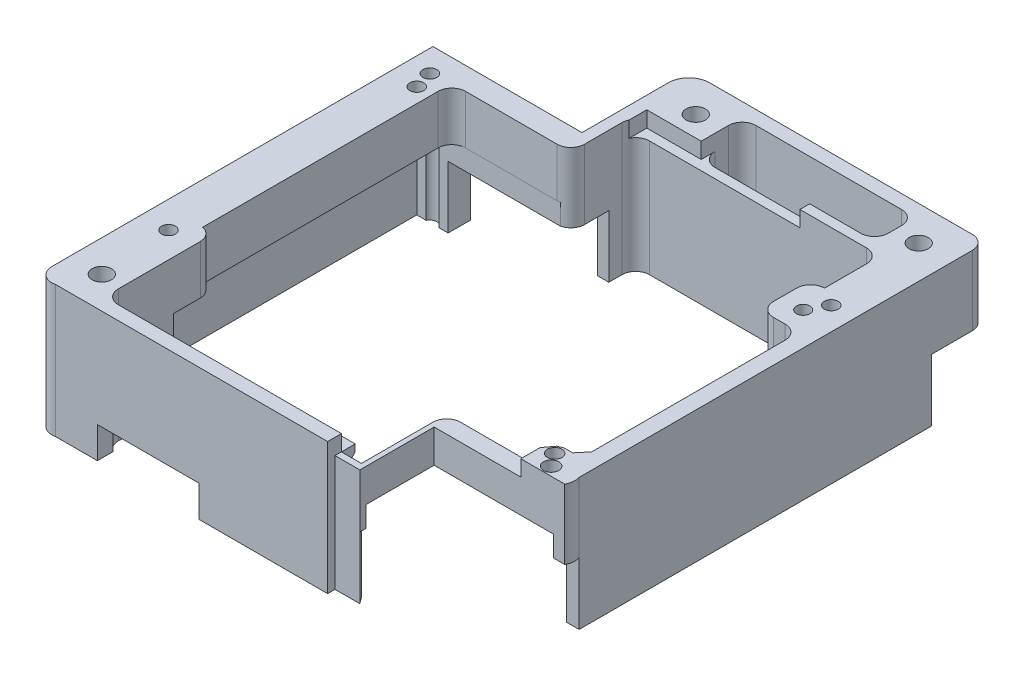
SolidWorks part; units mm, degrees
ref_plane "Спереди" through (0, 0, 0) normal (0, 0, 1) x (1, 0, 0)
ref_plane "Сверху" through (0, 0, 0) normal (0, 1, 0) x (1, 0, 0)
ref_plane "Справа" through (0, 0, 0) normal (1, 0, 0) x (0, 0, -1)
sketch "Sketch1" plane through (0, 0.1, 0) normal (0, -1, 0) x (1, 0, 0)
  line L0 (30.1923, -35.75) -> (30.1923, 21.25)
  line L1 (29.9933, 23.1419) -> (23.6204, 23.1419)
  line L2 (23.6204, 23.1419) -> (23.6204, 20.34)
  line L3 (23.6204, 20.34) -> (24.6552, 18.9626)
  line L4 (24.6552, 18.9626) -> (25.4, 18.6447)
  line L5 (25.4, 18.6447) -> (26.6442, 18.6447)
  line L6 (26.6442, 18.6447) -> (27.9, 17.1414)
  line L7 (27.9, 17.1414) -> (27.9, -12.9201)
  line L8 (27.9, -12.9201) -> (22.1982, -12.9201)
  line L9 (22.1982, -12.9201) -> (22.1982, -15.1177)
  line L10 (22.1982, -15.1177) -> (-28.5, -15.1177)
  line L14 (-28.5, -15.1177) -> (-28.5, 17.1414)
  line L15 (-28.5, 17.1414) -> (-26.8807, 17.1414)
  line L16 (-26.8807, 17.1414) -> (-26.8807, 26.25)
  line L17 (-26.8807, 26.25) -> (-26.8807, 34.9854)
  line L18 (-26.8807, 34.9854) -> (-31.9734, 34.9854)
  line L19 (-34.4999, 32.9854) -> (-34.5, -22.2395)
  line L20 (-34.5, -22.2395) -> (-12.89, -22.2395)
  line L21 (-12.89, -22.2395) -> (-12.89, -37.75)
  line L22 (-12.89, -37.75) -> (28.1923, -37.75)
  circle A0 centre (25.4, -32.7663) radius 1.4
  circle A1 centre (-6.9188, -32.7663) radius 1.4
  circle A2 centre (-29.9119, 30.3479) radius 1.4
  circle A3 centre (25.4, -16.0261) radius 0.9786
  circle A4 centre (-30.6214, -16.0261) radius 1
  circle A5 centre (25.4, 20.0142) radius 1.0496
  circle A6 centre (-30.6214, 19.9695) radius 1
  arc A7 (30.1923, -35.75) -> (28.1923, -37.75) centre (28.1923, -35.75) cw
  arc A8 (30.1923, 21.25) -> (29.9933, 23.1419) centre (27.8433, 21.9594) ccw
  arc A9 (-31.9734, 34.9854) -> (-34.4999, 32.9854) centre (-32.4675, 33.0137) ccw
  circle A10 centre (26.85, -18.6299) radius 1
  circle A11 centre (-31.3341, -18.6299) radius 1
  circle A13 centre (26.7535, 21.8701) radius 1.1
extrude "Boss-Extrude1" add sketch "Sketch1" along normal blind 3 and the other way blind 7.1
sketch "Sketch2" plane through (0, -2.9, 0) normal (0, -1, 0) x (1, 0, 0)
  line L0 (-26.8807, 17.1414) -> (-26.8807, 34.9854) construction
  line L2 (-26.8807, 34.9854) -> (-31.9734, 34.9854) construction
  line L8 (-26.8807, 32.9854) -> (-26.8807, 34.9854)
  line L14 (-26.8807, 34.9854) -> (7.4639, 34.9854)
  line L15 (7.4639, 34.9854) -> (7.4639, 32.9854)
  line L16 (7.4639, 32.9854) -> (-26.8807, 32.9854)
extrude "Boss-Extrude2" add sketch "Sketch2" against normal blind 10.1
sketch "Sketch5" plane through (0, 7.2, 0) normal (0, 1, 0) x (1, 0, 0)
  line L1 (-9.7084, -32.9854) -> (7.4639, -32.9854)
  line L2 (-9.7084, -32.9854) -> (-9.7084, -30.9854)
  line L3 (-9.7084, -30.9854) -> (7.4639, -30.9854)
  line L4 (7.4639, -32.9854) -> (7.4639, -30.9854)
extrude "Boss-Extrude5" add sketch "Sketch5" against normal blind 1 from offset 2.3 offset against normal yes
chamfer "Chamfer2" distance 2 angle 45 1 edges at (-1.1222, 3.9, 32.9854)
sketch "Sketch6" plane through (0, 7.2, 0) normal (0, 1, 0) x (1, 0, 0)
  line L2 (-11.0548, 29.8047) -> (-11.0548, 27.1518)
  line L7 (12.5536, 29.8047) -> (12.5536, 27.1518)
  line L12 (12.5536, 29.8047) -> (-11.0548, 29.8047)
  line L13 (-11.0548, 27.1518) -> (12.5536, 27.1518)
sketch "Sketch7" plane through (0, -2.9, 0) normal (0, -1, 0) x (1, 0, 0)
  line L0 (22.1982, -15.1177) -> (22.1982, -20.2902)
  line L1 (22.1982, -20.2902) -> (24.222, -20.2902)
  line L2 (24.222, -20.2902) -> (24.222, -28.3884)
  line L3 (22.1982, -15.1177) -> (-28.5, -15.1177) construction
  line L4 (22.1982, -12.9201) -> (22.1982, -15.1177) construction
  line L5 (24.222, -28.3884) -> (-11.2487, -28.3884)
  line L6 (-11.2487, -28.3884) -> (-11.2487, -18.9784)
  line L7 (-11.2487, -18.9784) -> (-28.5, -18.9784)
  line L9 (-28.5, -18.9784) -> (-28.5, -15.1177)
  line L10 (21.9508, -35.75) -> (21.9508, -29.8047)
  line L13 (21.9508, -29.8047) -> (-3.1678, -29.8047)
  line L14 (-3.1678, -29.8047) -> (-3.1678, -35.75)
  line L15 (-3.1678, -35.75) -> (21.9508, -35.75)
  line L16 (22.1982, -15.1177) -> (-28.5, -15.1177)
  dimension "D1" = 1.4163
extrude "Cut-Extrude1" cut sketch "Sketch7" against normal blind 21
extrude "Cut-Extrude2" cut sketch "Sketch6" against normal blind 2.3
sketch "Sketch8" plane through (0, -2.9, 0) normal (0, -1, 0) x (1, 0, 0)
  line L0 (23.6204, 23.1419) -> (11.0609, 23.1419)
  line L2 (11.0609, 23.1419) -> (11.0609, 33.9142)
  line L3 (11.0609, 33.9142) -> (7.4639, 33.9142)
  line L6 (7.4639, 33.9142) -> (7.4639, 32.9854)
  line L7 (7.4639, 32.9854) -> (10.3622, 32.9854)
  line L8 (10.3622, 32.9854) -> (10.3622, 20.6256)
  line L9 (10.3622, 20.6256) -> (23.6204, 20.6256)
  line L11 (23.6204, 20.6256) -> (23.6204, 23.1419)
  line L12 (7.4639, 32.9854) -> (7.4639, 34.9854) construction
  line L13 (29.9933, 23.1419) -> (23.6204, 23.1419) construction
  point P2 (11.0609, 23.1419)
extrude "Boss-Extrude6" add sketch "Sketch8" against normal up to surface (7.8 mm away) up to face at (-1.1222, 4.9, 31.9854)
fillet "Fillet1" radius 2 14 edges at (-28.5, 2.15, -18.9784) (21.9508, 2.15, -29.8047) (-3.1678, 1, -29.8047) (-3.1678, 2.15, -35.75) (21.9508, 2.15, -35.75) (22.1982, 2.15, -20.2902) (24.222, 2.15, -28.3884) (-11.2487, 2.15, -28.3884) (-11.2487, 2.15, -18.9784) (-26.8807, 2.15, 17.1414) (-26.8807, 2.15, 32.9854) (10.3622, 1, 20.6256) (22.1982, 2.15, -12.9201) (27.9, 2.15, -12.9201)
fillet "Fillet2" radius 3 1 edges at (-12.89, 2.15, -37.75)
sketch "Sketch9" plane through (0, -2.9, 0) normal (0, -1, 0) x (1, 0, 0)
  line L0 (-33.6214, 22.9739) -> (9.8918, 22.9739)
  line L1 (28.3786, -19.0261) -> (-33.6214, -19.0261)
  line L2 (28.3786, -19.0261) -> (28.3786, 22.9739)
  line L4 (-33.6214, -19.0261) -> (-33.6214, 22.9739)
  line L5 (9.8918, 22.9739) -> (9.8918, 32.9854)
  line L6 (9.8918, 32.9854) -> (28.3786, 32.9854)
  line L7 (28.3786, 32.9854) -> (28.3786, 22.9739)
  line L8 (-24.8807, 32.9854) -> (10.3622, 32.9854) construction
  circle A0 centre (-30.6214, -16.0261) radius 1 construction
  point P9 (9.8918, 32.9854)
  dimension "D1" = 62
  dimension "D2" = 42
  dimension "D3" = 3
  dimension "D4" = 3
extrude "Cut-Extrude3" cut sketch "Sketch9" against normal blind 3
sketch "Sketch10" plane through (0, -2.9, 0) normal (0, -1, 0) x (1, 0, 0)
  line L0 (30.1923, -29.8047) -> (-12.89, -29.8047)
  line L1 (30.1923, -35.75) -> (30.1923, 21.25) construction
  line L2 (-12.89, -22.2395) -> (-12.89, -34.75) construction
  line L3 (-12.89, -29.8047) -> (-12.89, -24.4887)
  line L5 (-34.5, -22.2395) -> (-34.4999, 32.9854)
  line L7 (-31.9734, 34.9854) -> (7.4639, 34.9854)
  line L8 (7.4639, 34.9854) -> (7.4639, 33.9142)
  line L9 (7.4639, 33.9142) -> (11.0609, 33.9142)
  line L12 (-30.416, -19.0261) -> (-12.8146, -19.0261) construction
  line L15 (30.1923, 21.25) -> (30.1923, -29.8047)
  line L16 (-33.6214, 22.9739) -> (-33.6214, -19.0261) construction
  line L17 (-29.0773, -19.0261) -> (-30.416, -19.0261)
  line L18 (-32.2523, -19.0261) -> (-33.6214, -19.0261)
  line L19 (10.3622, 32.9854) -> (11.0609, 33.9142)
  line L20 (30.1923, 21.25) -> (28.3786, 21.25)
  line L22 (28.3786, -19.0261) -> (28.3786, 23.1419) construction
  line L23 (28.3786, 21.25) -> (28.3786, -20.2902)
  line L24 (28.3786, -20.2902) -> (24.222, -20.2902)
  line L25 (24.222, -20.2902) -> (24.222, -26.3884)
  line L31 (-9.2487, -28.3884) -> (22.222, -28.3884)
  line L42 (10.3622, 32.9854) -> (10.3622, 23.3444) construction
  line L44 (-24.8807, 32.9854) -> (11.0609, 32.9854) construction
  line L45 (10.3622, 32.9854) -> (-24.8807, 32.9854)
  line L46 (-26.8807, 30.9854) -> (-26.8807, 28.6248)
  line L47 (-26.8807, 22.9739) -> (-26.8807, 30.9854) construction
  line L48 (-26.8807, 28.6248) -> (-33.6214, 28.6248)
  line L49 (-33.6214, 28.6248) -> (-33.6214, -19.0261)
  line L52 (-29.0773, -19.0261) -> (-29.0773, -22.2395)
  line L53 (-34.5, -22.2395) -> (-29.0773, -22.2395)
  line L54 (-11.2487, -26.3884) -> (-11.2487, -24.4887)
  line L55 (-11.2487, -20.9784) -> (-11.2487, -26.3884) construction
  line L56 (-11.2487, -24.4887) -> (-12.89, -24.4887)
  arc A1 (-34.4999, 32.9854) -> (-31.9734, 34.9854) centre (-32.4675, 33.0137) cw
  arc A2 (-30.416, -19.0261) -> (-32.2523, -19.0261) centre (-31.3341, -18.6299) cw
  arc A12 (22.222, -28.3884) -> (24.222, -26.3884) centre (22.222, -26.3884) ccw
  arc A13 (-9.2487, -28.3884) -> (-11.2487, -26.3884) centre (-9.2487, -26.3884) cw
  arc A14 (-24.8807, 32.9854) -> (-26.8807, 30.9854) centre (-24.8807, 30.9854) ccw
  circle A15 centre (-29.9119, 30.3479) radius 1.4
  circle A16 centre (27.4031, -26.3884) radius 1.4
extrude "Boss-Extrude7" add sketch "Sketch10" along normal blind 9
sketch "Sketch11" plane through (0, 0, 34.9854) normal (0, 0, 1) x (1, 0, 0)
  line L0 (7.4639, -11.9) -> (-31.9734, -11.9) construction
  line L1 (-11.1572, -11.9) -> (-25.9195, -11.9)
  line L2 (-11.1572, -11.9) -> (-11.1572, -7.3531)
  line L3 (-11.1572, -7.3531) -> (-25.9195, -7.3531)
  line L4 (-25.9195, -11.9) -> (-25.9195, -7.3531)
extrude "Cut-Extrude4" cut sketch "Sketch11" against normal blind 10
